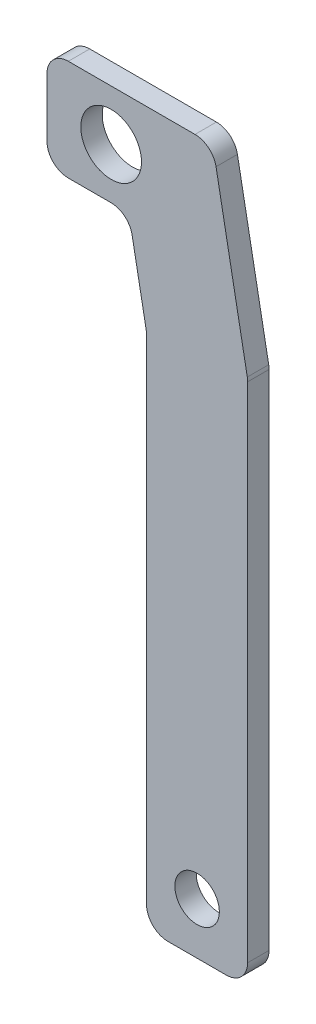
SolidWorks part; units mm, degrees
material "3003-H14"
ref_plane "X-Y Datum" through (0, 0, 0) normal (0, 0, 1) x (1, 0, 0)
ref_plane "X-Z Datum" through (0, 0, 0) normal (0, 1, 0) x (1, 0, 0)
ref_plane "Y-Z Datum" through (0, 0, 0) normal (1, 0, 0) x (0, 0, -1)
sketch "Sketch2" plane through (0, 0, 0) normal (0, 0, 1) x (1, 0, 0)
  line L0 (-160.8025, 213.9142) -> (-160.8025, 213.123) construction
  line L1 (-152.0649, 213.123) -> (-152.0649, 213.9142) construction
  line L2 (-160.8025, 213.9142) -> (-160.8025, 213.123) construction
  line L3 (-152.0649, 213.123) -> (-152.0649, 213.9142) construction
  line L4 (-160.8025, 213.5186) -> (-152.0649, 213.5186) construction
  line L5 (-156.4337, 221.0186) -> (-156.4337, 206.0186) construction
  line L6 (-151.1879, 122.9864) -> (-136.1879, 122.9864) construction
  line L7 (-156.4337, 206.0186) -> (-165.9587, 206.0186)
  line L8 (-165.9587, 206.0186) -> (-165.9587, 221.0186)
  line L9 (-165.9587, 221.0186) -> (-156.4337, 221.0186)
  line L10 (-151.1879, 122.9864) -> (-151.1879, 115.3664)
  line L11 (-151.1879, 115.3664) -> (-136.1879, 115.3664)
  line L12 (-136.1879, 115.3664) -> (-136.1879, 122.9864)
  line L13 (-156.4337, 206.0186) -> (-151.1879, 206.0186)
  line L14 (-151.1879, 206.0186) -> (-151.1879, 122.9864)
  line L15 (-136.1879, 122.9864) -> (-136.1879, 193.4446)
  line L16 (-141.365, 221.0186) -> (-156.4337, 221.0186)
  line L17 (-153.8108, 206.0186) -> (-151.1879, 192.0486)
  line L18 (-136.1879, 193.4446) -> (-141.365, 221.0186)
  circle A0 centre (-143.6879, 122.9864) radius 3 construction
  circle A1 centre (-143.6879, 122.9864) radius 3 construction
  arc A2 (-160.8025, 213.123) -> (-152.0649, 213.123) centre (-156.4337, 213.123) ccw construction
  arc A3 (-160.8025, 213.123) -> (-152.0649, 213.123) centre (-156.4337, 213.123) ccw construction
  arc A4 (-152.0649, 213.9142) -> (-160.8025, 213.9142) centre (-156.4337, 213.9142) ccw construction
  arc A5 (-152.0649, 213.9142) -> (-160.8025, 213.9142) centre (-156.4337, 213.9142) ccw construction
  point P14 (-156.4337, 213.5186)
  point P16 (-143.6879, 122.9864)
  dimension "D1" = 15
  dimension "D2" = 15
  dimension "D3" = 9.525
  dimension "D4" = 7.62
  dimension "D5" = 2.6229
  dimension "D6" = 13.97
  dimension "D7" = 15
extrude "Boss-Extrude1" add sketch "Sketch2" along normal blind 3.175 contours L15 L18 L16 L9 L8 L7 L13 L14 L10 L11 L12 | L13 L17 L14 region at (-145.8264, 172.1857, 0) region at (-152.0622, 201.3619, 0)
hole_wizard "M6 Clearance Hole1" positions "Sketch4" profile "Sketch5" hole size "M6" standard "ANSI Metric" end condition through all
sketch "Sketch4" plane through (0, 0, 3.175) normal (0, 0, 1) x (1, 0, 0)
  point P0 (-143.6879, 122.9864)
sketch "Sketch5" plane through (-143.6879, 122.9864, 3.175) normal (1, 0, 0) x (0, -1, 0)
  line L0 (0, 0) -> (0, 3.175)
  line L1 (0, 3.175) -> (3.3, 3.175)
  line L2 (3.3, 3.175) -> (3.3, 0)
  line L5 (3.3, 0) -> (0, 0)
  line L11 (0, -6.35) -> (0, 107.95) construction
  dimension "Thru Hole Dia." = 6.6
  dimension "Thru Hole Depth" = 3.175
fillet "Fillet1" radius 3.175 8 edges at (-151.1879, 192.0486, 1.5875) (-153.8108, 206.0186, 1.5875) (-141.365, 221.0186, 1.5875) (-136.1879, 193.4446, 1.5875) (-165.9587, 221.0186, 1.5875) (-165.9587, 206.0186, 1.5875) (-151.1879, 115.3664, 1.5875) (-136.1879, 115.3664, 1.5875)
hole_wizard "M8 Clearance Hole1" positions "Sketch6" profile "Sketch7" hole size "M8" standard "ANSI Metric" end condition through all
sketch "Sketch6" plane through (0, 0, 3.175) normal (0, 0, 1) x (1, 0, 0)
  point P0 (-156.4337, 213.5186)
sketch "Sketch7" plane through (-156.4337, 213.5186, 3.175) normal (1, 0, 0) x (0, -1, 0)
  line L0 (0, 0) -> (0, 3.175)
  line L1 (0, 3.175) -> (4.5, 3.175)
  line L2 (4.5, 3.175) -> (4.5, 0)
  line L5 (4.5, 0) -> (0, 0)
  line L11 (0, -6.35) -> (0, 107.95) construction
  dimension "Thru Hole Dia." = 9
  dimension "Thru Hole Depth" = 3.175
